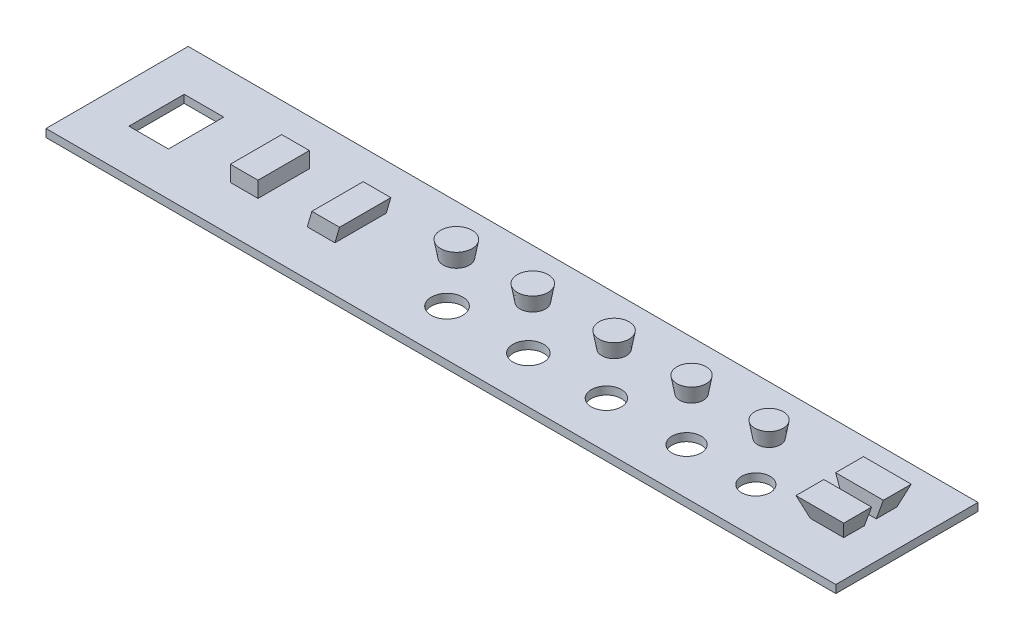
SolidWorks part; units mm, degrees
ref_plane "Front Plane" through (0, 0, 0) normal (0, 0, 1) x (1, 0, 0)
ref_plane "Top Plane" through (0, 0, 0) normal (0, 1, 0) x (1, 0, 0)
ref_plane "Right Plane" through (0, 0, 0) normal (1, 0, 0) x (0, 0, -1)
sketch "Sketch1" plane through (0, 0, 0) normal (0, 1, 0) x (1, 0, 0)
  line L0 (5, 9) -> (0, 9) construction
  line L1 (0, 0) -> (100, 0)
  line L2 (0, 0) -> (0, 18)
  line L3 (0, 18) -> (100, 18)
  line L4 (100, 0) -> (100, 18)
  line L5 (5, 12.5) -> (10, 12.5)
  line L6 (5, 12.5) -> (5, 5.5)
  line L7 (5, 5.5) -> (10, 5.5)
  line L8 (10, 12.5) -> (10, 5.5)
  line L9 (100, 9) -> (95, 9) construction
  line L10 (91.5, 9) -> (19.3401, 9)
  line L11 (91.5, 12) -> (95, 12)
  line L12 (91.5, 12) -> (91.5, 6)
  line L13 (91.5, 6) -> (95, 6)
  line L14 (95, 12) -> (95, 6)
  line L16 (21.0901, 5.75) -> (17.5901, 5.75)
  line L17 (21.0901, 5.75) -> (21.0901, 12.25)
  line L18 (21.0901, 12.25) -> (17.5901, 12.25)
  line L19 (17.5901, 5.75) -> (17.5901, 12.25)
  line L20 (21.0901, 5.75) -> (17.5901, 12.25) construction
  line L21 (21.0901, 12.25) -> (17.5901, 5.75) construction
  point P21 (19.3401, 9)
  dimension "D1" = 7
  dimension "D2" = 5
  dimension "D3" = 18
  dimension "D4" = 5
  dimension "D5" = 5
  dimension "D6" = 100
  dimension "D7" = 3.5
  dimension "D8" = 6
  dimension "D9" = 3.5
  dimension "D10" = 6.5
extrude "Boss-Extrude1" add sketch "Sketch1" along normal blind 1 contours L1 L4 L3 L2 L5 L8 L7 L6 L16 L19 L18 L17 L12 L11 L14 L13 region at (1.0161, 0, -9)
sketch "Sketch2" plane through (0, 0, 0) normal (0, -1, 0) x (1, 0, 0)
  line L4 (95, -6) -> (95, -12)
  line L5 (95, -12) -> (91.5, -12)
  line L6 (91.5, -12) -> (91.5, -6)
  line L7 (91.5, -6) -> (95, -6)
extrude "Boss-Extrude2" add sketch "Sketch2" against normal blind 3.5 draft 20 draft outward yes
sketch "Sketch3" plane through (0, 3.5, 0) normal (0, 1, 0) x (1, 0, 0)
  line L3 (90.2261, 9) -> (96.2739, 9) construction
  line L4 (90.2261, 4.7261) -> (90.2261, 13.2739) construction
  line L5 (96.2739, 13.2739) -> (96.2739, 4.7261) construction
  line L7 (90.2261, 8.25) -> (96.2739, 8.25)
  line L8 (90.2261, 8.25) -> (90.2261, 9.75)
  line L9 (90.2261, 9.75) -> (96.2739, 9.75)
  line L10 (96.2739, 8.25) -> (96.2739, 9.75)
  line L11 (90.2261, 8.25) -> (96.2739, 9.75) construction
  line L12 (90.2261, 9.75) -> (96.2739, 8.25) construction
  point P0 (40.971, 8.25)
  line M13 (96.2739, 4.7261) -> (96.2739, 13.2739)
  line M15 (90.2261, 13.2739) -> (90.2261, 4.7261)
  dimension "D1" = 1.5
extrude "Cut-Extrude1" cut sketch "Sketch3" against normal up to surface (2.5 mm away) contours L9 L7 M15 M13 region at (93.25, 3.5, -9) up to face at (93.25, 1, -9)
sketch "Sketch4" plane through (0, 0, 0) normal (0, -1, 0) x (1, 0, 0)
  line L0 (21.0901, -5.75) -> (17.5901, -5.75) construction
  line L1 (21.0901, -5.75) -> (21.0901, -12.25) construction
  line L2 (17.5901, -5.75) -> (17.5901, -12.25) construction
  line L3 (21.0901, -12.25) -> (17.5901, -12.25) construction
  line L4 (21.0901, -5.75) -> (17.5901, -5.75)
  line L5 (21.0901, -5.75) -> (21.0901, -12.25)
  line L6 (17.5901, -5.75) -> (17.5901, -12.25)
  line L7 (21.0901, -12.25) -> (17.5901, -12.25)
extrude "Boss-Extrude3" add sketch "Sketch4" against normal blind 3
sketch "Sketch9" plane through (0, 0, -12.25) normal (0, 0, -1) x (-1, 0, 0)
  line L0 (-31.4112, 3) -> (-27.9112, 3)
  line L1 (-17.5901, 3) -> (-21.0901, 3) construction
  line L2 (-31.4112, 3) -> (-30.5389, 0)
  line L3 (-30.5389, 0) -> (-27.0389, 0)
  line L4 (-27.0389, 0) -> (-27.9112, 3)
  line L5 (0, 0) -> (-100, 0) construction
  dimension "D1" = 3.5
extrude "Boss-Extrude4" add sketch "Sketch9" against normal up to surface (6.5 mm away) up to face at (19.3401, 2, -5.75)
sketch "Sketch10" plane through (0, 1, 0) normal (0, 1, 0) x (1, 0, 0)
  line L0 (100, 11.8146) -> (0, 11.8146) construction
  line L3 (100, 0) -> (100, 18) construction
  line L4 (0, 0) -> (0, 18) construction
  line L5 (100, 5.9012) -> (0, 5.9012) construction
  line L6 (0, 0) -> (100, 0) construction
  circle A0 centre (79.7275, 11.8146) radius 1.45
  circle A1 centre (69.9182, 11.8146) radius 1.5
  circle A2 centre (60.1089, 11.8146) radius 1.55
  circle A3 centre (49.8126, 11.8146) radius 1.6
  circle A4 centre (40.1424, 11.8146) radius 1.65
  circle A5 centre (83.9712, 5.9012) radius 1.8
  circle A6 centre (75.2054, 5.9012) radius 1.85
  circle A7 centre (65.0483, 5.9012) radius 1.9
  circle A8 centre (55.1694, 5.9012) radius 1.95
  circle A9 centre (44.8732, 5.9012) radius 2
  point P30 (100, 5.8316)
  point P31 (85.6409, 7.5709)
  point P32 (77.1534, 7.7796)
  point P33 (67.1354, 7.9187)
  point P34 (56.7695, 7.0143)
  point P35 (47.4472, 6.8752)
  point P36 (0, 0)
  point P37 (40.1424, 12.0233)
  point P38 (49.8126, 12.5103)
  point P39 (60.1089, 12.3712)
  point P40 (69.9182, 12.5103)
  point P41 (79.7275, 12.3712)
  point P42 (44.8732, 6.0403)
  point P43 (55.1694, 5.9012)
  point P44 (65.0483, 5.6229)
  point P45 (75.2054, 5.4142)
  point P46 (83.9712, 5.4142)
  dimension "D1" = 3.3
  dimension "D2" = 3.2
  dimension "D3" = 3.1
  dimension "D4" = 3
  dimension "D5" = 2.9
  dimension "D6" = 4
  dimension "D7" = 3.9
  dimension "D8" = 3.8
  dimension "D9" = 3.7
  dimension "D10" = 3.6
extrude "Cut-Extrude2" cut sketch "Sketch10" against normal through all contours A5 | A6 | A7 | A8 | A9
extrude "Boss-Extrude5" add sketch "Sketch10<3>" along normal blind 2 draft 10 contours A0 | A1 | A2 | A3 | A4 draft outward yes
sketch "Sketch10<3>" plane through (0, 1, 0) normal (0, 1, 0) x (1, 0, 0) same geometry as "Sketch10"
